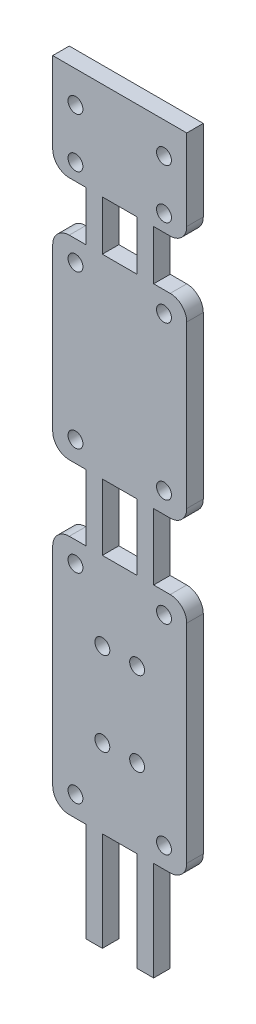
SolidWorks part; units mm, degrees
ref_plane "Front Plane" through (0, 0, 0) normal (0, 0, 1) x (1, 0, 0)
ref_plane "Top Plane" through (0, 0, 0) normal (0, 1, 0) x (1, 0, 0)
ref_plane "Right Plane" through (0, 0, 0) normal (1, 0, 0) x (0, 0, -1)
sketch "Sketch1" plane through (0, 0, 0) normal (0, 0, 1) x (1, 0, 0)
  line L0 (4, 26) -> (2, 26)
  line L1 (0, 1.5) -> (16.2, 1.5) construction
  line L2 (0, 14) -> (4, 14) construction
  line L3 (0, 14) -> (0, 1.5) construction
  line L4 (6, 14) -> (6, 26)
  line L5 (4, 14) -> (4, 26)
  line L6 (0, 28) -> (0, 53.14)
  line L7 (0, 94.665) -> (0, 104.46)
  line L8 (6, 14) -> (10.2, 14) construction
  line L9 (8.1, 1.5) -> (8.1, 104.46) construction
  line L10 (0, 104.46) -> (16.2, 104.46)
  line L11 (6, 63.14) -> (10.2, 63.14)
  line L12 (6, 55.14) -> (10.2, 55.14)
  line L13 (6, 92.665) -> (10.2, 92.665)
  line L14 (6, 86.665) -> (10.2, 86.665)
  line L15 (16.2, 84.665) -> (16.2, 65.14)
  line L16 (10.2, 86.665) -> (10.2, 92.665)
  line L17 (14.2, 55.14) -> (12.2, 55.14)
  line L18 (2, 92.665) -> (4, 92.665)
  line L19 (2, 86.665) -> (4, 86.665)
  line L20 (2, 63.14) -> (4, 63.14)
  line L21 (10.2, 55.14) -> (10.2, 63.14)
  line L22 (4, 86.665) -> (4, 92.665)
  line L23 (4, 55.14) -> (4, 63.14)
  line L24 (6, 55.14) -> (6, 63.14)
  line L25 (2, 55.14) -> (4, 55.14)
  line L26 (6, 86.665) -> (6, 92.665)
  line L27 (12.2, 55.14) -> (12.2, 63.14)
  line L28 (12.2, 86.665) -> (12.2, 92.665)
  line L29 (14.2, 63.14) -> (12.2, 63.14)
  line L30 (14.2, 86.665) -> (12.2, 86.665)
  line L31 (14.2, 92.665) -> (12.2, 92.665)
  line L32 (6, 26) -> (10.2, 26)
  line L33 (4, 14) -> (6, 14)
  line L34 (16.2, 94.665) -> (16.2, 104.46)
  line L35 (16.2, 28) -> (16.2, 53.14)
  line L36 (12.2, 14) -> (12.2, 26)
  line L37 (10.2, 14) -> (10.2, 26)
  line L38 (16.2, 14) -> (16.2, 1.5) construction
  line L39 (16.2, 14) -> (12.2, 14) construction
  line L40 (12.2, 26) -> (14.2, 26)
  line L41 (10.2, 14) -> (12.2, 14)
  line L58 (0, 84.665) -> (0, 65.14)
  circle A0 centre (2.85, 11.5) radius 0.9 construction
  circle A1 centre (13.45, 94.665) radius 0.9
  circle A2 centre (13.45, 84.165) radius 0.9
  circle A3 centre (2.85, 5.5) radius 0.9 construction
  circle A4 centre (13.45, 65.64) radius 0.9
  circle A5 centre (13.45, 52.64) radius 0.9
  circle A6 centre (13.45, 28.5) radius 0.9
  circle A7 centre (10.2, 35.5) radius 0.9
  arc A8 (16.2, 28) -> (14.2, 26) centre (14.2, 28) cw
  circle A9 centre (10.2, 45.64) radius 0.9
  arc A10 (2, 86.665) -> (0, 84.665) centre (2, 84.665) ccw
  arc A11 (14.2, 55.14) -> (16.2, 53.14) centre (14.2, 53.14) cw
  circle A12 centre (13.45, 100.665) radius 0.9
  arc A13 (16.2, 94.665) -> (14.2, 92.665) centre (14.2, 94.665) cw
  arc A14 (16.2, 65.14) -> (14.2, 63.14) centre (14.2, 65.14) cw
  arc A15 (0, 65.14) -> (2, 63.14) centre (2, 65.14) ccw
  arc A16 (0, 94.665) -> (2, 92.665) centre (2, 94.665) ccw
  arc A17 (14.2, 86.665) -> (16.2, 84.665) centre (14.2, 84.665) cw
  circle A18 centre (2.75, 100.665) radius 0.9
  circle A19 centre (13.35, 5.5) radius 0.9 construction
  circle A20 centre (13.35, 11.5) radius 0.9 construction
  arc A22 (2, 55.14) -> (0, 53.14) centre (2, 53.14) ccw
  circle A24 centre (6, 45.64) radius 0.9
  arc A26 (0, 28) -> (2, 26) centre (2, 28) ccw
  circle A30 centre (6, 35.5) radius 0.9
  circle A32 centre (2.75, 28.5) radius 0.9
  circle A34 centre (2.75, 52.64) radius 0.9
  circle A36 centre (2.75, 65.64) radius 0.9
  circle A38 centre (2.75, 84.165) radius 0.9
  circle A40 centre (2.75, 94.665) radius 0.9
  point P9 (8.1, 92.665)
  point P11 (8.1, 86.665)
  point P16 (8.1, 63.14)
  point P17 (8.1, 55.14)
  point P20 (8.1, 63.14)
  point P21 (8.1, 55.14)
  point P58 (8.1, 26)
  point P66 (8.1, 14)
  point P83 (8.1, 26)
  point P96 (8.1, 92.665)
  point P100 (8.1, 14)
  dimension "D8" = 2
  dimension "D28" = 2
  dimension "D30" = 2
  dimension "D32" = 2
  dimension "D42" = 1.8
  dimension "D44" = 2
  dimension "D2" = 2.85
  dimension "D3" = 4
  dimension "D4" = 2.85
  dimension "D5" = 6
  dimension "D6" = 2.5
  dimension "D7" = 12
  dimension "D9" = 2.5
  dimension "D10" = 9.5
  dimension "D11" = 2.75
  dimension "D13" = 2.5
  dimension "D14" = 9.5
  dimension "D15" = 2.75
  dimension "D17" = 29.14
  dimension "D12" = 6
  dimension "D16" = 6
  dimension "D18" = 2.75
  dimension "D19" = 2.5
  dimension "D20" = 8
  dimension "D21" = 2
  dimension "D22" = 2
  dimension "D23" = 2
  dimension "D24" = 2
  dimension "D25" = 2.75
  dimension "D26" = 2.5
  dimension "D27" = 23.525
  dimension "D39" = 2
  dimension "D40" = 2.75
  dimension "D41" = 6
  dimension "D45" = 2.75
  dimension "D46" = 6
  dimension "D47" = 11.795
  dimension "D48" = 8.1
  dimension "D49" = 2
extrude "Boss-Extrude1" add sketch "Sketch1" along normal blind 2
sketch "Sketch2" plane through (0, 0, 2) normal (0, 0, 1) x (1, 0, 0)
  line L0 (4, 92.665) -> (12.2, 92.665)
  line L1 (12.2, 92.665) -> (12.2, 86.665)
  line L2 (12.2, 86.665) -> (4, 86.665)
  line L3 (4, 86.665) -> (4, 92.665)
  line L4 (4, 63.14) -> (12.2, 63.14)
  line L5 (12.2, 63.14) -> (12.2, 55.14)
  line L6 (12.2, 55.14) -> (4, 55.14)
  line L7 (4, 55.14) -> (4, 63.14)
  line L8 (4, 26) -> (12.2, 26)
  line L9 (12.2, 26) -> (12.2, 14)
  line L10 (12.2, 14) -> (4, 14)
  line L11 (4, 14) -> (4, 26)
extrude "Cut-Extrude1" [suppressed] cut sketch "Sketch2" against normal up to surface (2 mm away) up to face at (3.65, 94.665, 0)
equation "\"D48@Sketch1\"= ( \"fingerWidth@parametersSketch@prostheticParameters.SLDPRT\" ) / 2 'Ring Width"
equation "\"D17@Sketch1\"= \"HL@parametersSketch@prostheticParameters.SLDPRT\" * 0.244 - 4 - 12'Ring PIP Length"
equation "\"D27@Sketch1\"= \"HL@parametersSketch@prostheticParameters.SLDPRT\" * 0.165 - 3 - 4'Ring MIP Length"
equation "\"D47@Sketch1\"= \"HL@parametersSketch@prostheticParameters.SLDPRT\" * 0.107 - 3 - 5'Ring DIP Length - Gap fingertip"
equation "\"D42@Sketch1\"= 1.5 + \"tol1@parametersSketch@prostheticParameters.SLDPRT\""
